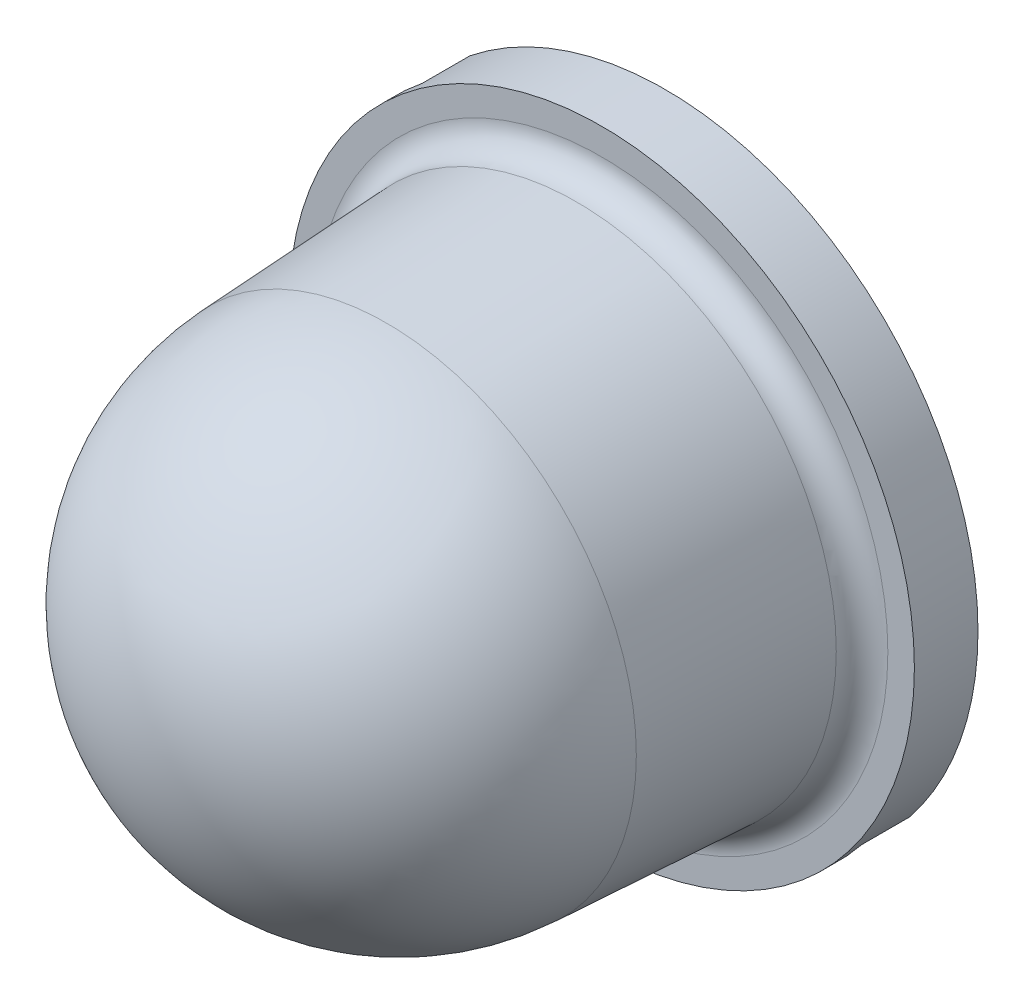
SolidWorks part; units mm, degrees
material "ABS"
ref_plane "Front" through (0, 0, 0) normal (0, 0, 1) x (1, 0, 0)
ref_plane "Top" through (0, 0, 0) normal (0, 1, 0) x (1, 0, 0)
ref_plane "Right" through (0, 0, 0) normal (1, 0, 0) x (0, 0, -1)
sketch "Эскиз1" plane through (0, 0, 0) normal (0, 1, 0) x (1, 0, 0)
  line L0 (-5.9, 0) -> (-4.8, 0)
  line L1 (-4.8, 0) -> (-4.8, -0.7)
  line L2 (-4.8, -0.7) -> (-4.1, -0.7)
  line L3 (-4.1, -0.7) -> (-4.1, -5.0114)
  line L4 (0, -9.1114) -> (0, -9.73)
  line L6 (-4.7121, -5.2583) -> (-4.9, -1.6738)
  line L8 (-5.9, -1.2) -> (-5.9, 0)
  line L9 (0, -9.1114) -> (0, 0) construction
  line L10 (-5.9, -1.2) -> (-5.3993, -1.2)
  arc A0 (-4.1, -5.0114) -> (0, -9.1114) centre (0, -5.0114) ccw
  arc A2 (-4.7121, -5.2583) -> (0, -9.73) centre (0, -5.0114) ccw
  arc A3 (-5.3993, -1.2) -> (-4.9, -1.6738) centre (-5.3993, -1.7) cw
  dimension "D1" = 11.8
  dimension "D5" = 3
  dimension "D6" = 0.5
  dimension "D2" = 9.73
  dimension "D3" = 1.2
  dimension "D4" = 8.2
  dimension "D7" = 9.6
  dimension "D8" = 0.7
  dimension "D9" = 9.8
revolve "Повернуть1" add sketch "Эскиз1" angle 360 about L9
sketch "Эскиз4" plane through (0, 0, 0) normal (0, 0, -1) x (-1, 0, 0)
  line L0 (-3.7123, -4.6315) -> (-2.9032, -3.8225)
  line L2 (-3.8225, -2.9032) -> (-4.6315, -3.7123)
  line L3 (-4.6315, -3.7123) -> (-3.7123, -4.6315)
  line L4 (-4.1719, -4.1719) -> (4.1719, 4.1719) construction
  line L5 (2.9032, 3.8225) -> (3.7123, 4.6315)
  line L6 (3.7123, 4.6315) -> (4.6315, 3.7123)
  line L7 (4.6315, 3.7123) -> (3.8225, 2.9032)
  line L9 (0, 0) -> (0, -2.2379) construction
  circle A1 centre (0, 0) radius 4.8 construction
  circle A2 centre (0, 0) radius 5.9 construction
  circle A3 centre (0, 0) radius 5.9 construction
  arc A4 (-2.9032, -3.8225) -> (-3.8225, -2.9032) centre (0, 0) cw
  arc A5 (2.9032, 3.8225) -> (3.8225, 2.9032) centre (0, 0) cw
  dimension "D1" = 1.3
  dimension "D2" = 45
extrude "Вырез-Вытянуть2" cut sketch "Эскиз4" against normal blind 0.9
sketch "Рабочаа область" plane through (0, 0, 0) normal (0, 1, 0) x (1, 0, 0)
  line L0 (0, -4.7) -> (0, -18.1411) construction
  line L1 (0, -4.7) -> (37.6815, -26.4554)
  line L2 (26.5004, -20) -> (26.5004, 0)
  line L3 (0, 0) -> (26.5004, 0) construction
  line L6 (3.7231, 0) -> (-3.7231, 0) construction
  line L7 (3.7231, 0) -> (3.7231, -4.7) construction
  line L8 (3.7231, -4.7) -> (-3.7231, -4.7) construction
  line L9 (-3.7231, 0) -> (-3.7231, -4.7) construction
  line L10 (3.7231, 0) -> (-3.7231, -4.7) construction
  line L11 (3.7231, -4.7) -> (-3.7231, 0) construction
  point P11 (0, -2.35)
  point P12 (0, 0)
  point P13 (-0.0048, -4.8191)
  point P14 (0, 0)
  point P15 (0, -4.7)
  dimension "D1" = 60
  dimension "D2" = 20
  dimension "D3" = 4.7
  dimension "D4" = 53.0008
